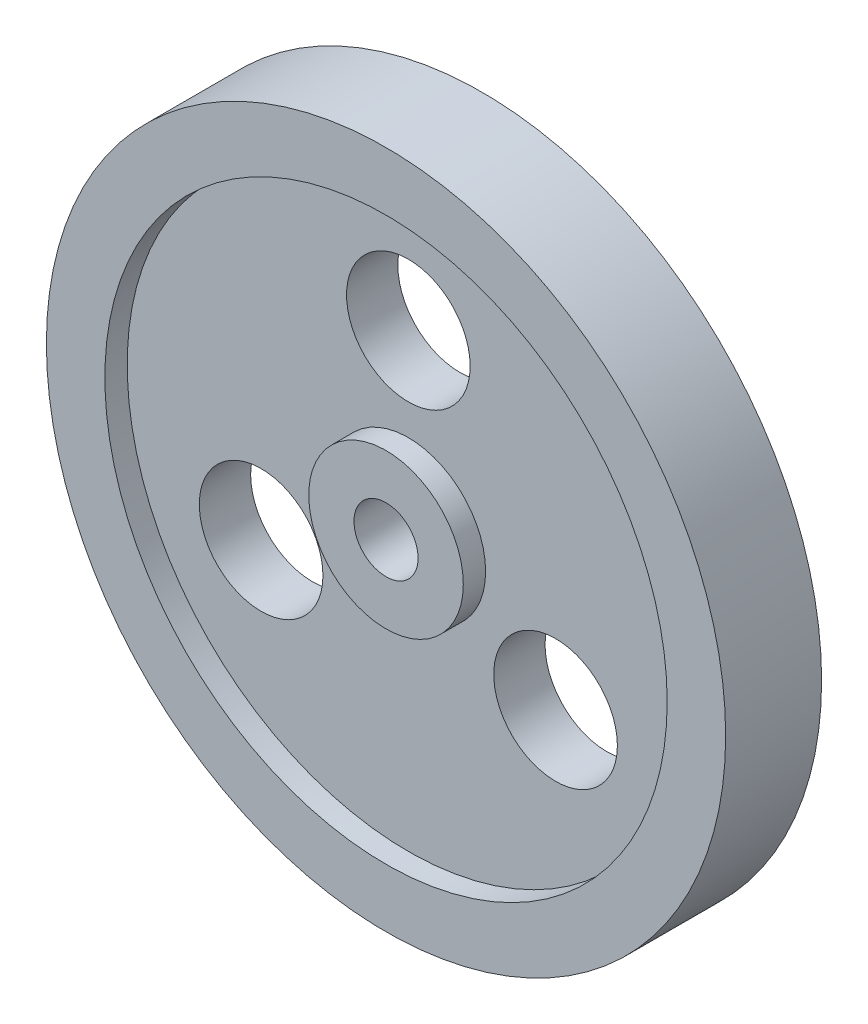
SolidWorks part; units mm, degrees
ref_plane "Front Plane" through (0, 0, 0) normal (0, 0, 1) x (1, 0, 0)
ref_plane "Top Plane" through (0, 0, 0) normal (0, 1, 0) x (1, 0, 0)
ref_plane "Right Plane" through (0, 0, 0) normal (1, 0, 0) x (0, 0, -1)
sketch "Sketch1" plane through (0, 0, 0) normal (0, 0, 1) x (1, 0, 0)
  circle A0 centre (0, 0) radius 19.781
  circle A1 centre (0, 0) radius 1.8669
  dimension "D1" = 39.5619
  dimension "D2" = 3.7338
extrude "Boss-Extrude1" add sketch "Sketch1" along normal mid plane 5.588
sketch "Sketch2" plane through (0, 0, 2.794) normal (0, 0, 1) x (1, 0, 0)
  circle A0 centre (0, 0) radius 16.375
  circle A1 centre (0, 0) radius 4.5
  dimension "D1" = 32.75
  dimension "D2" = 9
extrude "Cut-Extrude1" cut sketch "Sketch2" against normal blind 1.3
mirror "Mirror1" about plane through (0, 0, 0) normal (0, 0, 1) of "Cut-Extrude1"
sketch "Sketch3" plane through (0, 0, 1.494) normal (0, 0, 1) x (1, 0, 0)
  line L0 (0, 0) -> (0, 10.8598)
  circle A0 centre (0, 9.9) radius 3.6
  circle A1 centre (8.5737, -4.95) radius 3.6
  circle A2 centre (-8.5737, -4.95) radius 3.6
  point P9 (0, 0)
  point P11 (0, 0)
  point P12 (-10.0353, -3.4158)
  point P13 (0, 0)
  dimension "D1" = 7.2
  dimension "D2" = 9.9
  dimension "D3" = 3
extrude "Cut-Extrude2" cut sketch "Sketch3" against normal through all contours A2 | A1 | A0 region at (2.4736, 7.4264, 1.494) region at (8.5737, -4.95, 1.494) region at (-8.5737, -4.95, 1.494)
